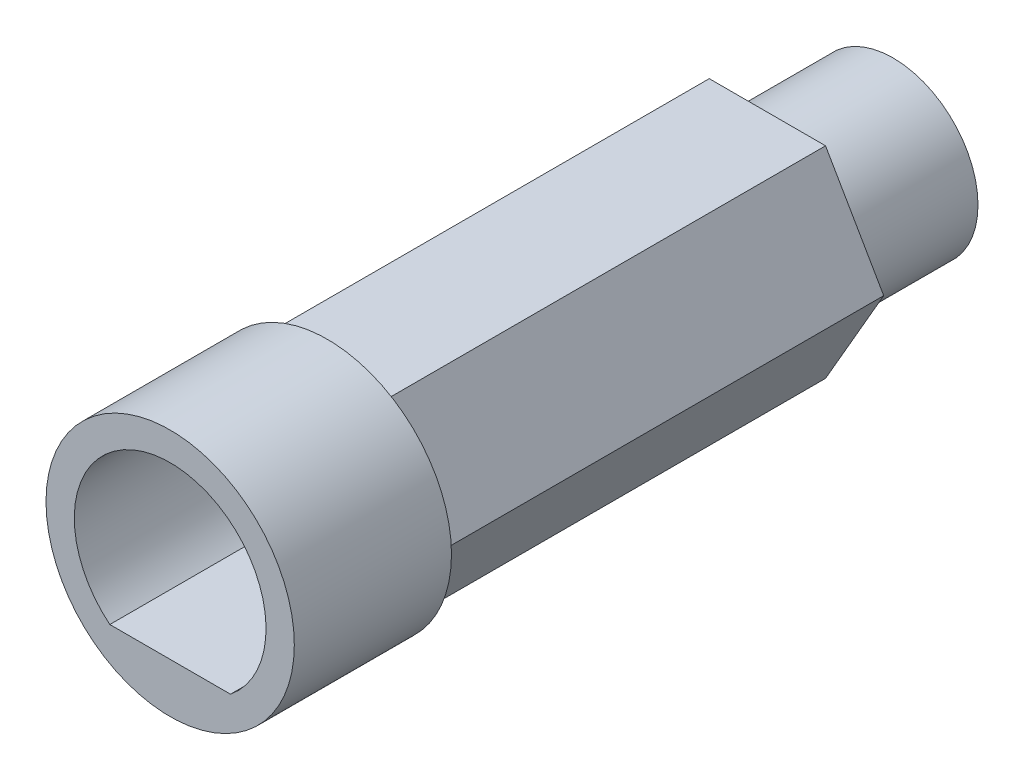
SolidWorks part; units mm, degrees
ref_plane "Front Plane" through (0, 0, 0) normal (0, 0, 1) x (1, 0, 0)
ref_plane "Top Plane" through (0, 0, 0) normal (0, 1, 0) x (1, 0, 0)
ref_plane "Right Plane" through (0, 0, 0) normal (1, 0, 0) x (0, 0, -1)
sketch "Sketch1" plane through (0, 0, 0) normal (0, 0, 1) x (1, 0, 0)
  line L1 (3.7, 0) -> (1.85, 3.2043)
  line L2 (1.85, 3.2043) -> (-1.85, 3.2043)
  line L3 (-1.85, 3.2043) -> (-3.7, 0)
  line L4 (-3.7, 0) -> (-1.85, -3.2043)
  line L5 (-1.85, -3.2043) -> (1.85, -3.2043)
  line L6 (1.85, -3.2043) -> (3.7, 0)
  circle A0 centre (0, 0) radius 3.7 construction
  circle A1 centre (0, 0) radius 3.2043 construction
  dimension "D1" = 7.4
extrude "Boss-Extrude1" add sketch "Sketch1" along normal blind 14
sketch "Sketch2" plane through (0, 0, 14) normal (0, 0, 1) x (1, 0, 0)
  circle A0 centre (0, 0) radius 3.95
  dimension "D1" = 7.9
extrude "Boss-Extrude2" add sketch "Sketch2" along normal blind 5
sketch "Sketch3" plane through (0, 0, 0) normal (0, 0, -1) x (-1, 0, 0)
  circle A0 centre (0, 0) radius 2.7
  dimension "D1" = 5.4
extrude "Boss-Extrude3" add sketch "Sketch3" along normal blind 4
sketch "Sketch4" plane through (0, 0, 19) normal (0, 0, 1) x (1, 0, 0)
  line L0 (-1.9198, -2.37) -> (1.9198, -2.37)
  circle A0 centre (0, 0) radius 3.05
  point P5 (-1.8, -2.4)
  point P6 (1.8, -2.4)
  dimension "D1" = 6.1
  dimension "D2" = 5.42
extrude "Cut-Extrude1" cut sketch "Sketch4" against normal blind 16 contours L0 A0 region at (0, 0.1719, 19)
